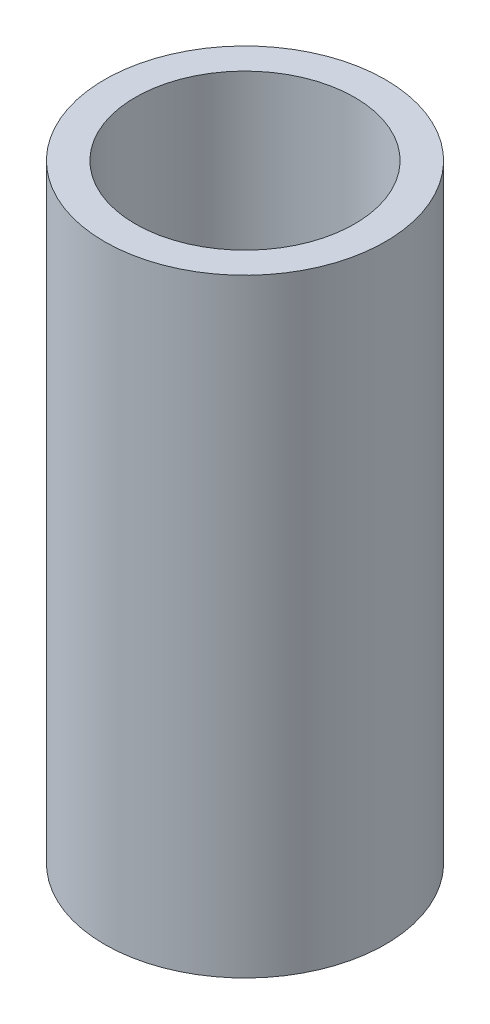
SolidWorks part; units mm, degrees
ref_plane "Front Plane" through (0, 0, 0) normal (0, 0, 1) x (1, 0, 0)
ref_plane "Top Plane" through (0, 0, 0) normal (0, 1, 0) x (1, 0, 0)
ref_plane "Right Plane" through (0, 0, 0) normal (1, 0, 0) x (0, 0, -1)
sketch "Sketch1" plane through (0, 0, 0) normal (0, 1, 0) x (1, 0, 0)
  circle A0 centre (0, 0) radius 17.5
  dimension "SLEEVE_OD" = 35
extrude "Boss-Extrude1" add sketch "Sketch1" along normal blind 75.8408
sketch "Sketch2" plane through (0, 0, 0) normal (0, 1, 0) x (1, 0, 0)
  circle A0 centre (0, 0) radius 13.67
  dimension "BORE_D" = 27.3399
extrude "Cut-Extrude1" cut sketch "Sketch2" along normal through all
chamfer "Chamfer1" distance 2.8217 angle 31.232 rebuild error yes
